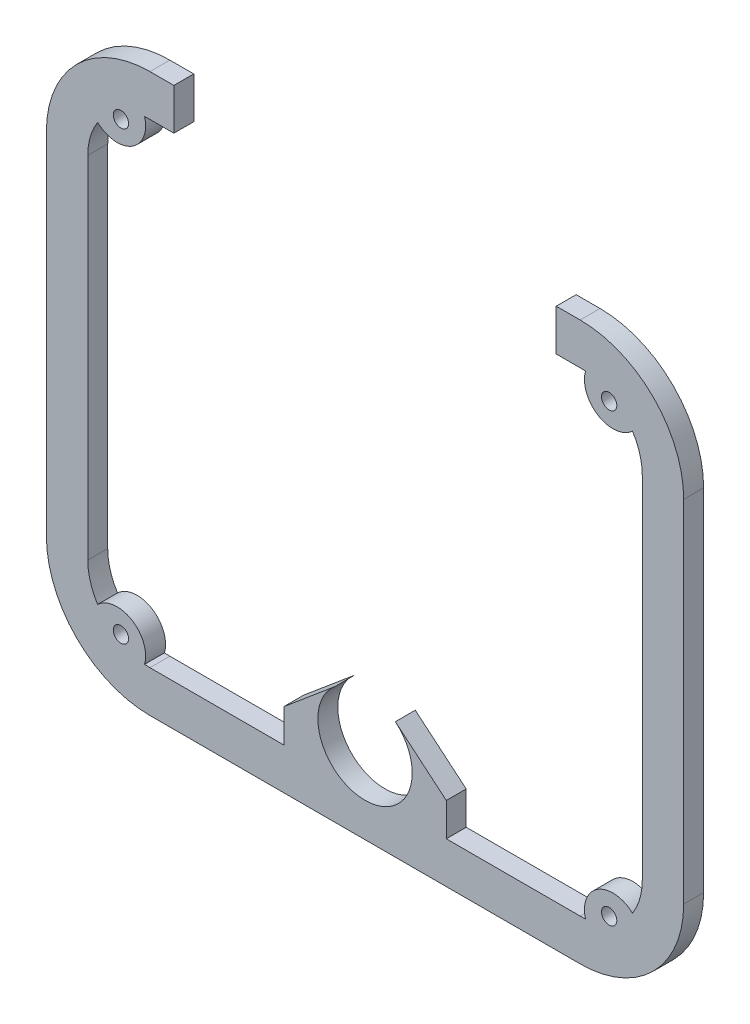
SolidWorks part; units mm, degrees
material "Delrin"
ref_plane "Front Plane" through (0, 0, 0) normal (0, 0, 1) x (1, 0, 0)
ref_plane "Top Plane" through (0, 0, 0) normal (0, 1, 0) x (1, 0, 0)
ref_plane "Right Plane" through (0, 0, 0) normal (1, 0, 0) x (0, 0, -1)
sketch "Sketch1" plane through (0, 0, 0) normal (0, 0, 1) x (1, 0, 0)
  line L0 (-17.145, -18.923) -> (-9.6321, -18.923)
  line L1 (17.145, 22.225) -> (-17.145, 22.225)
  line L2 (25.4, 13.97) -> (25.4, -13.97)
  line L3 (17.145, -22.225) -> (-17.145, -22.225)
  line L4 (-25.4, 13.97) -> (-25.4, -13.97)
  line L5 (25.4, 22.225) -> (-25.4, -22.225) construction
  line L6 (25.4, -22.225) -> (-25.4, 22.225) construction
  line L7 (9.6321, -18.923) -> (17.145, -18.923)
  line L10 (-22.098, 13.97) -> (-22.098, -13.97)
  line L11 (-1000, 0) -> (49000, 0) construction
  line L13 (22.098, 13.97) -> (22.098, -13.97)
  line L14 (17.145, 18.923) -> (-17.145, 18.923)
  line L18 (0, 18.923) -> (0, -18.415) construction
  line L21 (2.4164, -12.8683) -> (9.6321, -18.923)
  line L22 (-2.4164, -12.8683) -> (-9.6321, -18.923)
  line L36 (17.145, -18.923) -> (-17.145, -18.923) construction
  arc A0 (-2.4164, -12.8683) -> (2.4164, -12.8683) centre (0, -15.748) ccw
  arc A1 (-17.145, 22.225) -> (-25.4, 13.97) centre (-17.145, 13.97) ccw
  arc A2 (17.145, 22.225) -> (25.4, 13.97) centre (17.145, 13.97) cw
  arc A3 (25.4, -13.97) -> (17.145, -22.225) centre (17.145, -13.97) cw
  arc A4 (-17.145, -22.225) -> (-25.4, -13.97) centre (-17.145, -13.97) cw
  arc A5 (-21.3168, 16.6398) -> (-17.5714, 18.9046) centre (-19.7605, 18.2953) ccw
  arc A6 (21.3168, 16.6398) -> (17.5714, 18.9046) centre (19.7605, 18.2953) cw
  arc A7 (17.145, 18.923) -> (22.098, 13.97) centre (17.145, 13.97) cw
  arc A8 (-17.145, 18.923) -> (-22.098, 13.97) centre (-17.145, 13.97) ccw
  circle A9 centre (-19.4575, 17.78) radius 0.6096
  circle A10 centre (19.4575, 17.78) radius 0.6096
  circle A11 centre (-19.4575, -17.78) radius 0.6096
  circle A12 centre (19.4575, -17.78) radius 0.6096
  arc A13 (-17.145, -18.923) -> (-22.098, -13.97) centre (-17.145, -13.97) cw construction
  arc A14 (22.098, -13.97) -> (17.145, -18.923) centre (17.145, -13.97) cw construction
  arc A15 (-22.098, -13.97) -> (-17.145, -18.923) centre (-17.145, -13.97) ccw
  arc A16 (17.145, -18.923) -> (22.098, -13.97) centre (17.145, -13.97) ccw
  arc A17 (21.3168, -16.6398) -> (17.5714, -18.9046) centre (19.7605, -18.2953) ccw
  arc A18 (-21.3168, -16.6398) -> (-17.5714, -18.9046) centre (-19.7605, -18.2953) cw
  point P0 (0, 0)
  dimension "D4" = 7.5184
  dimension "D6" = 8.255
  dimension "D7" = 8.255
  dimension "D8" = 8.255
  dimension "D9" = 8.255
  dimension "D5" = 1.2192
  dimension "D1" = 50.8
  dimension "D2" = 44.45
  dimension "D10" = 3.302
  dimension "D3" = 3.175
  dimension "D11" = 17.78
  dimension "D12" = 19.4575
  dimension "D13" = 15.748
extrude "Boss-Extrude1" add sketch "Sketch1" along normal blind 1.5875 contours A4 L3 A3 L2 A2 L1 A1 L4 A16 L7 L21 A0 L22 L0 A15 A11 L10 A8 A9 L14 A7 A10 L13 A12 | A9 A8 A5 | A16 A17 A12 | A18 A15 A11 | A7 A10 A6 region at (-18.4919, -18.6865, 0) region at (-20.7018, 17.3477, 0) region at (18.6095, -16.3919, 0) region at (18.4919, 18.6865, 0) region at (22.5049, 19.3299, 0)
sketch "Sketch2" plane through (0, 0, 1.5875) normal (0, 0, 1) x (1, 0, 0)
  line L1 (-9.6321, -18.923) -> (-6.477, -18.923)
  line L2 (-9.6321, -18.923) -> (-9.6321, -16.2756)
  line L3 (-9.6321, -16.2756) -> (-6.477, -16.2756)
  line L4 (-6.477, -18.923) -> (-6.477, -16.2756)
  line L5 (0, -1000) -> (0, 49000) construction
  line L6 (9.6321, -18.923) -> (9.6321, -16.2756)
  line L7 (9.6321, -16.2756) -> (6.477, -16.2756)
  line L8 (6.477, -18.923) -> (6.477, -16.2756)
  line L9 (9.6321, -18.923) -> (6.477, -18.923)
  line L11 (-15.24, 18.923) -> (15.24, 18.923)
  line L12 (-15.24, 18.923) -> (-15.24, 22.225)
  line L13 (-15.24, 22.225) -> (15.24, 22.225)
  line L14 (15.24, 18.923) -> (15.24, 22.225)
  line L16 (17.145, 18.923) -> (-17.145, 18.923) construction
  line L17 (-2.4164, -12.8683) -> (-9.6321, -18.923) construction
  line L18 (17.145, 22.225) -> (-17.145, 22.225) construction
  point P25 (0, 22.225)
  dimension "D1" = 6.477
  dimension "D2" = 30.48
extrude "Cut-Extrude1" cut sketch "Sketch2" against normal up to next
